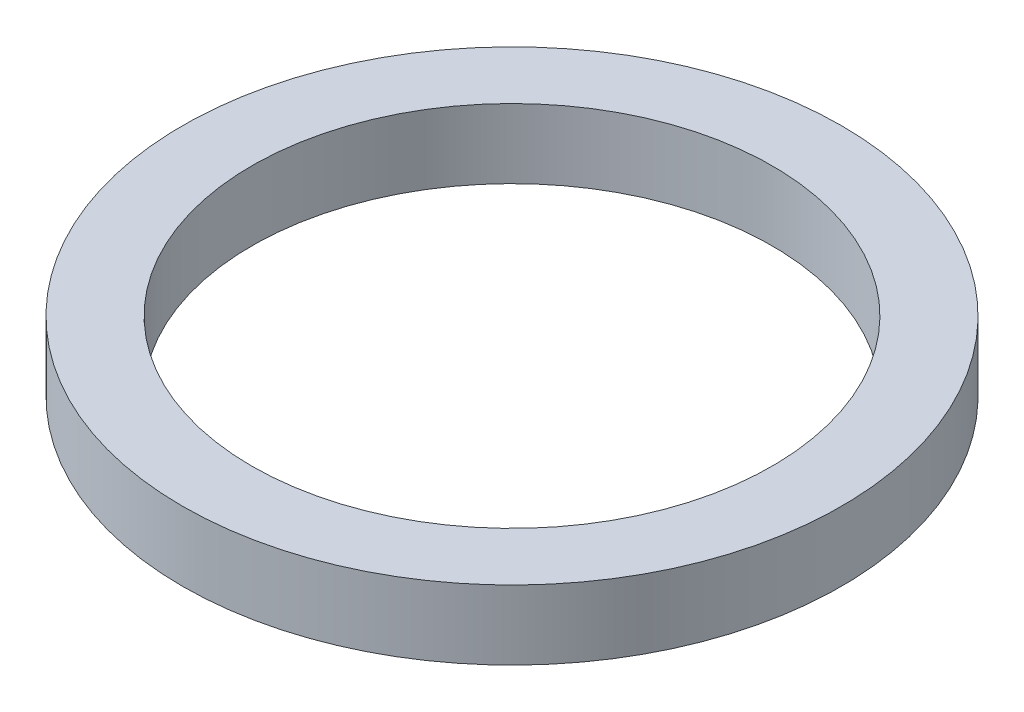
SolidWorks part; units mm, degrees
ref_plane "Front Plane" through (0, 0, 0) normal (0, 0, 1) x (1, 0, 0)
ref_plane "Top Plane" through (0, 0, 0) normal (0, 1, 0) x (1, 0, 0)
ref_plane "Right Plane" through (0, 0, 0) normal (1, 0, 0) x (0, 0, -1)
sketch "Sketch1" plane through (0, 0, 0) normal (0, 1, 0) x (1, 0, 0)
  circle A0 centre (0, 0) radius 37.5
  circle A1 centre (0, 0) radius 47.5
  dimension "D1" = 75
  dimension "D2" = 95
extrude "Boss-Extrude1" add sketch "Sketch1" along normal mid plane 10
equation "\"module\" = 0.5"
equation "\"pressure_angle\" = 20.0"
equation "\"h_a\" = 0.5"
equation "\"h_f\" = 0.625"
equation "\"clr_tip_root\" = 0.125"
equation "\"bearing_ID\" = 75"
equation "\"bearing_OD\" = 95"
equation "\"bearing_height\" = 10"
equation "\"clearance_planet\" = 1.5"
equation "\"case_dist\" = 6.5"
equation "\"Motor_case_OD_max\" = 131.3"
equation "\"case_mounting_PCD\" = 123.8"
equation "\"bearing mount thickness\" = 8"
equation "\"case_mounting_hole_dia\" = 3"
equation "\"output_mounting_PCD\" = 103"
equation "\"output_mounting_hole_dia\" = 4"
equation "\"clearance_case_mount_holes_shell_thickness\" = 1"
equation "\"motor_case_OD_base\" = 121.8"
equation "\"sec_carrier_thickness\" = 5"
equation "\"sun_coupler_hub_thickness\" = 4"
equation "\"clearance_sun_coupler_sec_carrier\" = 1.5"
equation "\"clearance_motor_and_case\" = 5"
equation "\"motor_OD\" = 106.8"
equation "\"Motor_case_thickness\" = 2.5"
equation "\"Motor_case_ID\" = 116.8"
equation "\"case_mounting_hole_shift\" = 1.0"
equation "\"output_mounting_nut_wrench_size\" = 7"
equation "\"output_mounting_nut_thickness\" = 3.2"
equation "\"case_mounting_hole_allen_socket_dia\" = 5.5"
equation "\"output_mounting_nut_depth\" = 3"
equation "\"case_mounting_bolt_depth\" = 4.5"
equation "\"Ns\" = 80"
equation "\"ring_radial_thickness\" = 5"
equation "\"ring_to_chamfer_clearance\" = 1.5"
equation "\"Motor_case_OD_base_to_chamfer\" = 5"
equation "\"pattern_offset_from_motor_case_OD_base\" = 3"
equation "\"pattern_bulge_dia\" = 3"
equation "\"pattern_num_bulge\" = 18"
equation "\"pattern_depth\" = 2"
equation "\"motor_height\" = 47.6"
equation "\"case_mounting_wrench_size\" = 5.5"
equation "\"case_mounting_nut_clearance\" = 2"
equation "\"base_plate_thickness\" = 4"
equation "\"case_mounting_nut_thickness\" = 2.4"
equation "\"case_mounting_surface_height\" = 4"
equation "\"motor_mount_hole_PCD\" = 40"
equation "\"motor_mount_hole_dia\" = 5"
equation "\"motor_mount_hole_num\" = 4"
equation "\"central_hole_offset_from_motor_mount_PCD\" = 5"
equation "\"wire_slot_dist_from_center\" = 45.5"
equation "\"wire_slot_length\" = 10"
equation "\"wire_slot_radius\" = 3"
equation "\"driver_upper_holes_dist_from_center\" = 29"
equation "\"driver_lower_holes_dist_from_center\" = 13"
equation "\"driver_side_holes_dist_from_center\" = 22.5"
equation "\"driver_mount_holes_dia\" = 3"
equation "\"driver_mount_inserts_OD\" = 4.8"
equation "\"driver_mount_thickness\" = 1.5"
equation "\"driver_mount_height\" = 6"
equation "\"air_flow_hole_offset\" = 3"
equation "\"num_planet\" = 5"
equation "\"planet_pin_bolt_dia\" = 5"
equation "\"planet_pin_socket_head_dia\" = 8.5"
equation "\"carrier_PCD\" = 67.5"
equation "\"planet_shaft_dia\" = 8"
equation "\"planet_shaft_step_offset\" = 1"
equation "\"carrier_trapezoidal_support_sun_offset\" = 5"
equation "\"carrier_trapezoidal_support_hole_PCD_offset_bearing_ID\" = 4"
equation "\"carrier_trapezoidal_support_hole_dia\" = 3"
equation "\"carrier_trapezoidal_support_hole_socket_head_dia\" = 5.5"
equation "\"carrier_bearing_step_width\" = 1.5"
equation "\"standard_clearance_1_5mm\" = 1.5"
equation "\"standard_fillet_1_5mm\" = 1.5"
equation "\"sun_shaft_bearing_OD\" = 16"
equation "\"sun_shaft_bearing_width\" = 5"
equation "\"standard_bearing_insertion_chamfer\" = 0.5"
equation "\"D1@Sketch1\"=\"bearing_ID\""
equation "\"D2@Sketch1\"=\"bearing_OD\""
equation "\"D1@Boss-Extrude1\"=\"bearing_height\""
equation "\"carrier_trapezoidal_support_hole_wrench_size\" = 5.5"
equation "\"planet_pin_bolt_wrench_size\" = 8"
equation "\"Np_b\" = 55"
equation "\"pressure angle\" = 20.0"
equation "\"h_b\" = 0.625"
equation "\"dp_s\" = 40.0"
equation "\"db_s\" = 37.58770483143634"
equation "\"fw_s_calc\" = 4.872946430626146"
equation "\"alpha_s\" = 0.8539582918412272"
equation "\"beta_s\" = 0.5420834163175456"
equation "\"dp_p_b\" = 27.5"
equation "\"db_p_b\" = 25.84154707161248"
equation "\"fw_p_s\" = 15.81085678360617"
equation "\"alpha_p_b\" = 0.8539582918412449"
equation "\"beta_p_b\" = 1.564810689044783"
equation "\"planet_bearing_OD\" = 12"
equation "\"planet_bearing_width\" = 3.5"
equation "\"planet_bore\" = 10"
equation "\"motor_output_hole_PCD\" = 23"
equation "\"motor_output_hole_dia\" = 4"
equation "\"motor_output_hole_num\" = 4"
equation "\"sun_shaft_bearing_ID\" = 8"
equation "\"sun_hub_dia\" = 30.0"
equation "\"sun_central_bolt_dia\" = 5"
equation "\"sun_central_bolt_socket_head_dia\" = 8.5"
equation "\"fw_s_used\" = 44.67596466627659"
equation "\"motor_output_hole_CSK_OD\" = 8"
equation "\"motor_output_hole_CSK_head_height\" = 2.0"
equation "\"bearing_retainer_thickness\" = 2"
equation "\"Np_s\" = 35"
equation "\"fw_p_b\" = 21.365107882670422"
equation "\"dp_p_s\" = 17.5"
equation "\"db_p_s\" = 16.444620863753396"
equation "\"alpha_p_s\" = 0.8539582918412556"
equation "\"beta_p_s\" = 3.434940559174632"
equation "\"Nr_b\" = 190"
equation "\"dp_r_b\" = 95.0"
equation "\"db_r_b\" = 89.2707989746613"
equation "\"fw_r_b\" = 21.365107882670422"
equation "\"alpha_r_b\" = 0.8539582918412414"
equation "\"beta_r_b\" = 2.655285004735114"
equation "\"ring_OD_b\" = 105.0"
equation "\"Fillet10\"= IIF ( \"ring_OD_b\" > ( \"bearing_OD\" + 2 * \"bearing mount thickness\" ) , \"suppressed\" , \"unsuppressed\" )"
equation "\"Fillet11\"= IIF ( \"ring_OD_b\" < ( \"bearing_OD\" + 2 * \"bearing mount thickness\" ) , \"suppressed\" , \"unsuppressed\" )"
equation "\"Nr_s\" = 170"
equation "\"clr_tip_root_s\" = 0.125"
equation "\"dp_r_s\" = 85.0"
equation "\"db_r_s\" = 79.87387276680222"
equation "\"fw_r_s\" = 14.31085678360617"
equation "\"alpha_r_s\" = 0.8539582918412307"
equation "\"beta_r_s\" = 2.766740113094226"
equation "\"small_ring_case_thickness\" = 4"
equation "\"carrier_thickness\" = 4"
equation "\"small_ring_output_wall_thickness\" = 5"
equation "\"small_ring_output_wall_to_bearing_shaft_attachement_hole_dia\" = 4"
equation "\"small_ring_output_wall_to_bearing_shaft_attachement_hole_depth\" = 6.5"
equation "\"small_ring_output_wall_to_bearing_shaft_attachement_nut_wrench\" = 7"
equation "\"small_ring_output_wall_to_bearing_shaft_attachement_nut_thickness\" = 3.2"
equation "\"small_ring_output_wall_to_bearing_shaft_attachement_hole_pcd\" = 12"
equation "\"small_ring_output_wall_to_bearing_shaft_attachement_hole_num\" = 3"
equation "\"small_ring_output_wall_to_bearing_shaft_attachement_hole_CSK_OD\" = 8"
equation "\"small_ring_output_wall_to_bearing_shaft_attachement_hole_CSK_head_height\" = 2.0"
equation "\"carrier_small_ring_inner_bearing_ID\" = 20"
equation "\"carrier_small_ring_inner_bearing_OD\" = 32"
equation "\"carrier_small_ring_inner_bearing_height\" = 7"
equation "\"carrier_small_ring_inner_bearing_flap\" = 2"
equation "\"gear_casing_big_ring_to_bearing_dist\" = 24.81085678360617"
equation "\"gear_casing_thickness\" = 4"
